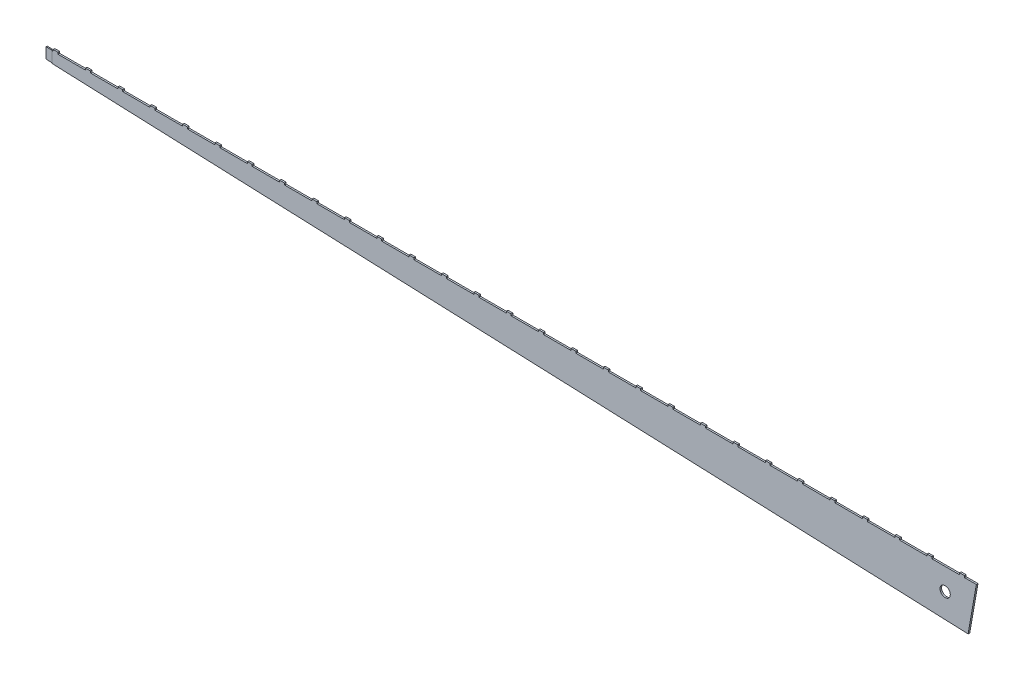
SolidWorks part; units mm, degrees
ref_plane "front" through (0, 0, 0) normal (0, 0, 1) x (1, 0, 0)
ref_plane "top" through (0, 0, 0) normal (0, 1, 0) x (1, 0, 0)
ref_plane "right" through (0, 0, 0) normal (1, 0, 0) x (0, 0, -1)
ref_axis "Axis1" through (-4.2838, 0, 0) along (1, 0, 0)
sketch "Sketch1" plane through (0, 0, 0) normal (0, 0, 1) x (1, 0, 0)
  line L0 (128.4732, 0) -> (566.7248, 0)
  line L1 (566.7248, 0) -> (562.8256, -22.1135)
  line L2 (562.8256, -22.1135) -> (128.4732, -5.0477)
  line L3 (128.4732, -5.0477) -> (128.4732, 0)
  line L4 (0, 0) -> (128.4732, -11.2399) construction
  line L5 (0, 0) -> (128.4732, -22.6533) construction
  circle A0 centre (552.0149, -10.2877) radius 2.4257
  circle A1 centre (129.9972, -1.397) radius 0.6223 construction
  circle A2 centre (129.9972, -3.683) radius 0.6223 construction
  dimension "D8" = 4.8514
  dimension "D11" = 1.2446
  dimension "D12" = 1.524
  dimension "D15" = 2.286
  dimension "D1" = 5
  dimension "D2" = 2.25
  dimension "D3" = 128.4732
  dimension "D4" = 438.2516
  dimension "D5" = 10
  dimension "D6" = 558.115
  dimension "D7" = 566.7248
  dimension "D9" = 10.2877
  dimension "D10" = 12.7
  dimension "D13" = 1.397
  dimension "D14" = 85.725
extrude "Extrude1" add sketch "Sketch1" along normal mid plane 0.762
sketch "Sketch2" plane through (0, 0, 0) normal (0, 0, 1) x (1, 0, 0)
  line L1 (132.08, 0.8128) -> (134.366, 0.8128)
  line L2 (132.08, 0.8128) -> (132.08, -0.254)
  line L3 (132.08, -0.254) -> (134.366, -0.254)
  line L4 (134.366, 0.8128) -> (134.366, -0.254)
  dimension "D1" = 0.8128
  dimension "D2" = 0.254
  dimension "D3" = 132.08
  dimension "D4" = 2.286
extrude "EB-02 Tab 1" add sketch "Sketch2" along normal mid plane 0.762
pattern_linear "LP-01 Tab 1 x 29 x 0.600" count 29 spacing 15.24 along (1, 0, 0) of "EB-02 Tab 1"
sketch "Sketch3" [suppressed] plane through (0, 0, 0) normal (0, 0, 1) x (1, 0, 0)
  line L0 (610.0727, 19.8325) -> (435.0938, 19.8325)
  line L1 (435.0938, 19.8325) -> (423.2444, -47.369)
  line L2 (423.2444, -47.369) -> (610.0727, -47.369)
  line L3 (610.0727, -47.369) -> (610.0727, 19.8325)
  line L4 (0, 0) -> (128.4732, -22.6533) construction
  line L5 (128.4732, 0) -> (566.7248, 0) construction
  circle A0 centre (420.2289, -9.6181) radius 2.4257
  point P2 (431.5968, 0)
  dimension "D3" = 4.8514
  dimension "D6" = 63.5
  dimension "D1" = 431.5968
  dimension "D2" = 425.0399
  dimension "D4" = 9.6181
  dimension "D5" = 9.525
extrude "Extrude3" [suppressed] cut sketch "Sketch3" against normal mid plane 2.54
sketch "Sketch4" plane through (0, 0, 0) normal (0, 1, 0) x (1, 0, 0)
  line L1 (127.9652, 0.1473) -> (131.5212, 0.1473)
  line L2 (127.9652, 0.1473) -> (127.9652, -0.1473)
  line L3 (127.9652, -0.1473) -> (131.5212, -0.1473)
  arc A0 (131.5212, -0.1473) -> (131.5212, 0.1473) centre (131.5212, 0) ccw
  point P4 (127.9652, 0)
  dimension "D3" = 3.048
  dimension "D1" = 0.2946
  dimension "D2" = 0.508
extrude "Extrude4" [suppressed] cut sketch "Sketch4" against normal mid plane 15.24
sketch "Sketch5" plane through (0, 0, 0.381) normal (0, 0, 1) x (1, 0, 0)
  line L0 (128.4732, -5.0477) -> (128.4732, 0) construction
  line L1 (125.0514, 2.0876) -> (131.5212, 2.0876)
  line L2 (125.0514, 2.0876) -> (125.0514, -6.6657)
  line L3 (125.0514, -6.6657) -> (131.5212, -6.6657)
  line L4 (131.5212, 2.0876) -> (131.5212, -6.6657)
  dimension "D1" = 3.048
extrude "Extrude5" cut sketch "Sketch5" against normal blind 0.254
sketch "Sketch6" [suppressed] plane through (0, 0, -0.381) normal (0, 0, -1) x (-1, 0, 0)
  line L0 (-567.8231, -22.2409) -> (-567.8231, 11.6354)
